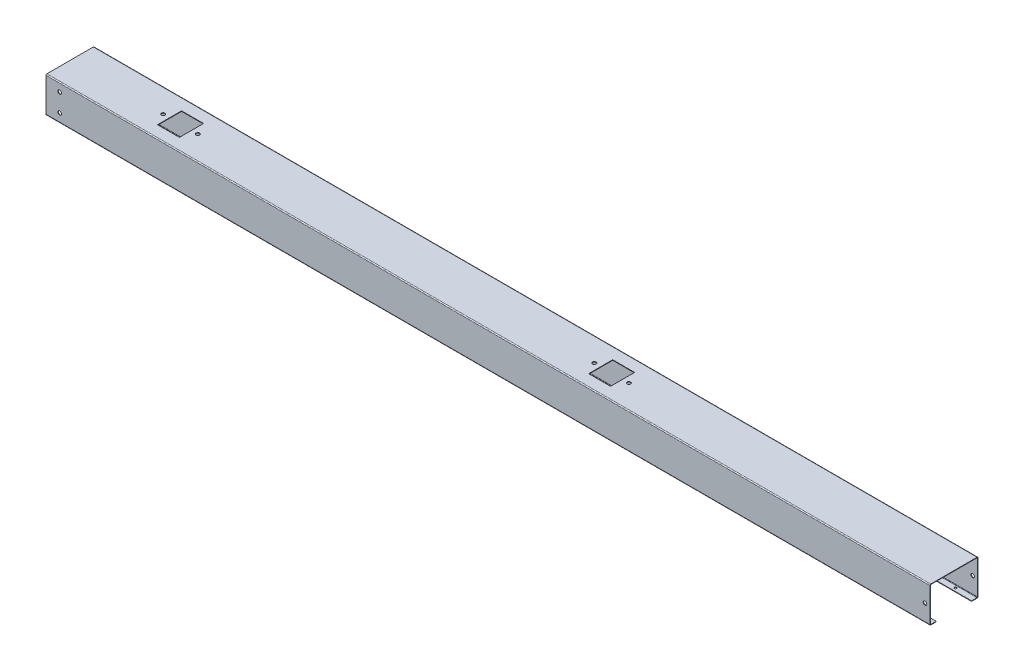
SolidWorks part; units mm, degrees
note: The reader was unsure of these and kept them because the rebuilt part matched: thickness of "Base-Flange1", "Edge-Flange1", "Edge-Flange5", "Sheet-Metal1", "Sheet-Metal2", "Sheet-Metal3", "Sheet-Metal5", "Sheet-Metal15", "Sheet-Metal16", "Sheet-Metal17", "Sheet-Metal22", "Sheet-Metal28", "Sheet-Metal29"; flange length of "Edge-Flange1", "Edge-Flange5".
ref_plane "Front Plane" through (0, 0, 0) normal (0, 0, 1) x (1, 0, 0)
ref_plane "Top Plane" through (0, 0, 0) normal (0, 1, 0) x (1, 0, 0)
ref_plane "Right Plane" through (0, 0, 0) normal (1, 0, 0) x (0, 0, -1)
sketch "Sketch1" plane through (0, 0, 0) normal (0, 1, 0) x (1, 0, 0)
  line L0 (825.5, 38.1) -> (825.5, -38.1)
  line L1 (-571.5, -38.1) -> (825.5, -38.1)
  line L2 (-571.5, -38.1) -> (-571.5, 38.1)
  line L3 (-571.5, 38.1) -> (825.5, 38.1)
  point P0 (0, 0)
  dimension "D1" = 1397
  dimension "D2" = 76.2
base flange "Base-Flange1" sketch "Sketch1" thickness 0.7595 reverse thickness direction no parameters "D1"=0.7366
sketch "Sketch6" plane through (0, 0, 0) normal (0, 1, 0) x (1, 0, 0)
  line L1 (-414.3375, -19.05) -> (-390.7165, -19.05)
  line L2 (-414.3375, -19.05) -> (-414.3375, 19.05)
  line L3 (-414.3375, 19.05) -> (-390.7165, 19.05)
  line L4 (-379.6665, -19.05) -> (-379.6665, 19.05)
  line L5 (-414.3375, -19.05) -> (-379.6665, 19.05) construction
  line L6 (-414.3375, 19.05) -> (-379.6665, -19.05) construction
  line L7 (267.1445, -19.05) -> (290.7655, -19.05)
  line L8 (267.1445, -19.05) -> (267.1445, 19.05)
  line L9 (267.1445, 19.05) -> (290.7655, 19.05)
  line L10 (301.8155, -19.05) -> (301.8155, 19.05)
  line L11 (267.1445, -19.05) -> (301.8155, 19.05) construction
  line L12 (267.1445, 19.05) -> (301.8155, -19.05) construction
  line L13 (-390.7165, 19.05) -> (-379.6665, 19.05)
  line L14 (-390.7165, -19.05) -> (-379.6665, -19.05)
  line L15 (290.7655, 19.05) -> (301.8155, 19.05)
  line L16 (290.7655, -19.05) -> (301.8155, -19.05)
  line L17 (-571.5, 38.1) -> (-571.5, -38.1) construction
  point P0 (-397.002, 0)
  point P6 (284.48, 0)
  point P15 (-414.3375, 0)
  point P19 (267.1445, 0)
  point P23 (-379.6665, 0)
  point P28 (301.8155, 0)
  dimension "D1" = 34.671
  dimension "D2" = 38.1
  dimension "D3" = 34.671
  dimension "D4" = 38.1
  dimension "D5" = 174.498
  dimension "D6" = 681.482
extrude "Cut-Extrude1" cut sketch "Sketch6" against normal blind 10 normal cut yes
sketch "Sketch7" plane through (0, 0, 0) normal (0, 1, 0) x (1, 0, 0)
  line L0 (-414.3375, 19.05) -> (-414.3375, -19.05) construction
  line L1 (-379.6665, -19.05) -> (-379.6665, 19.05) construction
  line L2 (267.1445, -19.05) -> (267.1445, 19.05) construction
  line L4 (301.8155, -19.05) -> (301.8155, 19.05) construction
  circle A0 centre (-424.3375, 0) radius 2.8194
  circle A1 centre (-369.6665, 0) radius 2.8194
  circle A4 centre (257.1445, 0) radius 2.8194
  circle A5 centre (311.8155, 0) radius 2.8194
  dimension "D1" = 5.6388
  dimension "D2" = 10
  dimension "D4" = 5.6388
  dimension "D8" = 5.6388
  dimension "D9" = 5.6388
  dimension "D3" = 10
  dimension "D5" = 10
  dimension "D7" = 10
extrude "Cut-Extrude2" cut sketch "Sketch7" against normal blind 10 normal cut yes
edge flange "Edge-Flange1" sketch "Sketch37" flange profiles "Sketch37", "Sketch39" flange angle 90 flange length 55.372 flange position material inside bend radius 0.7366 thickness 0.7595 relief rectangular parameters "D6"=10, "D8"=0.254
sketch "Sketch37" plane through (0, -0.7595, -38.1) normal (0, 0, -1) x (1, 0, 0)
  line L0 (825.5, 0) -> (-571.5, 0) construction
  line L1 (825.5, 0) -> (-571.5, 0)
  line L2 (-571.5, 0) -> (-571.5, 54.6125)
  line L3 (-571.5, 54.6125) -> (825.5, 54.6125)
  line L4 (825.5, 54.6125) -> (825.5, 0)
sketch "Sketch39" plane through (0, -0.7595, 38.1) normal (0, 0, 1) x (-1, 0, 0)
  line L0 (571.5, 0) -> (-825.5, 0) construction
  line L1 (571.5, 0) -> (-825.5, 0)
  line L2 (-825.5, 0) -> (-825.5, 54.6125)
  line L3 (-825.5, 54.6125) -> (571.5, 54.6125)
  line L4 (571.5, 54.6125) -> (571.5, 0)
bend "EdgeBend8" bend radius 0.7366 bend angle 90 parameters "D5"=4
bend "EdgeBend9" bend radius 0.7366 bend angle 90 parameters "D5"=5
sketch "Sketch40" plane through (0, 0, -38.1) normal (0, 0, -1) x (-1, 0, 0)
  line L0 (543.46, -13.448) -> (556.16, -13.448) construction
  line L1 (543.46, -10.6286) -> (556.16, -10.6286)
  line L2 (543.46, -16.2674) -> (556.16, -16.2674)
  line L3 (571.5, -1.4961) -> (571.5, 0) construction
  line L4 (571.5, -55.372) -> (571.5, -1.4961) construction
  arc A0 (543.46, -10.6286) -> (543.46, -16.2674) centre (543.46, -13.448) ccw
  arc A1 (556.16, -16.2674) -> (556.16, -10.6286) centre (556.16, -13.448) ccw
  point P2 (549.81, -13.448)
  point P9 (571.5, -0.748)
  dimension "D1" = 12.7
  dimension "D2" = 5.6388
  dimension "D3" = 12.7
  dimension "D4" = 21.69
extrude "Cut-Extrude3" [suppressed] cut sketch "Sketch40" against normal through all both and the other way through all
sketch "Sketch42" plane through (0, 0, 38.1) normal (0, 0, 1) x (1, 0, 0)
  line L0 (-571.5, -1.4961) -> (-571.5, -55.372) construction
  line L1 (-571.5, -55.372) -> (825.5, -55.372) construction
  circle A0 centre (-127, -21.082) radius 2.8194
  circle A1 centre (-76.2, -21.082) radius 2.8194
  dimension "D3" = 5.6388
  dimension "D1" = 444.5
  dimension "D2" = 34.29
  dimension "D4" = 50.8
extrude "Cut-Extrude4" [suppressed] cut sketch "Sketch42" against normal up to next
sketch "Sketch43" plane through (0, 0, -38.1) normal (0, 0, -1) x (-1, 0, 0)
  line L0 (571.5, -55.372) -> (571.5, -1.4961) construction
  line L1 (571.5, -1.4961) -> (571.5, 0) construction
  line L2 (-825.5, -55.372) -> (571.5, -55.372) construction
  circle A0 centre (549.91, -13.448) radius 2.8194
  circle A1 centre (549.91, -42.164) radius 2.8194
  point P6 (571.5, -0.748)
  dimension "D3" = 5.6388
  dimension "D1" = 21.59
  dimension "D2" = 12.7
  dimension "D4" = 21.59
  dimension "D5" = 13.208
extrude "Cut-Extrude5" cut sketch "Sketch43" against normal through all both and the other way through all normal cut yes
edge flange "Edge-Flange5" sketch "Sketch85" flange profiles "Sketch85", "Sketch87" flange angle 90 flange length 10.16 flange position material outside bend radius 0.7366 thickness 0.7595 relief rectangular parameters "D6"=10, "D8"=0.254
sketch "Sketch85" plane through (0, -55.372, 37.3405) normal (0, 1, 0) x (1, 0, 0)
  line L2 (-571.5, 0) -> (-571.5, 9.4005)
  line L3 (-571.5, 9.4005) -> (825.5, 9.4005)
  line L4 (825.5, 9.4005) -> (825.5, 0)
  line L5 (825.5, 0) -> (-571.5, 0) construction
  line L6 (825.5, 0) -> (-571.5, 0)
sketch "Sketch87" plane through (0, -55.372, -37.3405) normal (0, 1, 0) x (-1, 0, 0)
  line L0 (571.5, 0) -> (-825.5, 0) construction
  line L1 (571.5, 0) -> (-825.5, 0)
  line L2 (571.5, 0) -> (571.5, 9.4005)
  line L3 (571.5, 9.4005) -> (-825.5, 9.4005)
  line L4 (-825.5, 9.4005) -> (-825.5, 0)
bend "EdgeBend15" bend radius 0.7366 bend angle 90 parameters "D5"=6
bend "EdgeBend16" bend radius 0.7366 bend angle 90 parameters "D5"=8
sketch "Sketch133" plane through (0, -56.1315, 0) normal (0, -1, 0) x (1, 0, 0)
  line L0 (825.5, 36.6039) -> (825.5, 27.94) construction
  line L1 (825.5, 36.6039) -> (-571.5, 36.6039) construction
  line L2 (825.5, -36.6039) -> (-571.5, -36.6039) construction
  circle A0 centre (698.5, -32.7939) radius 1.651
  circle A1 centre (698.5, 32.7939) radius 1.651
  circle A2 centre (201.93, 32.7939) radius 1.651
  circle A3 centre (201.93, -32.7939) radius 1.651
  circle A4 centre (-238.76, -32.7939) radius 1.651
  circle A5 centre (-238.76, 32.7939) radius 1.651
  circle A6 centre (-467.36, 32.7939) radius 1.651
  circle A7 centre (-467.36, -32.7939) radius 1.651
  circle A8 centre (-535.94, 32.7939) radius 1.651
  circle A9 centre (-535.94, -32.7939) radius 1.651
  circle A10 centre (795.02, 32.7939) radius 1.651
  circle A11 centre (795.02, -32.7939) radius 1.651
  dimension "D1" = 3.302
  dimension "D2" = 127
  dimension "D3" = 3.81
  dimension "D4" = 3.81
  dimension "D5" = 496.57
  dimension "D6" = 440.69
  dimension "D7" = 228.6
  dimension "D8" = 68.58
  dimension "D9" = 96.52
extrude "Cut-Extrude6" cut sketch "Sketch133" against normal up to next and the other way through all normal cut yes
sketch "Sketch134" plane through (0, 0, -38.1) normal (0, 0, -1) x (-1, 0, 0)
  line L0 (-825.5, -1.4961) -> (-825.5, -54.6354) construction
  line L1 (-825.5, 0) -> (571.5, 0) construction
  circle A0 centre (-817.88, -29.21) radius 2.8194
  dimension "D1" = 5.6388
  dimension "D2" = 7.62
  dimension "D3" = 29.21
extrude "Cut-Extrude7" cut sketch "Sketch134" against normal through all both and the other way through all normal cut yes
sketch "Bend-Lines1" [suppressed] plane through (0, 0, 0) normal (0, 1, 0) x (1, 0, 0)
sketch "Bounding-Box1" [suppressed] plane through (0, 0, 0) normal (0, 1, 0) x (1, 0, 0)
sheet metal parameters "Sheet-Metal1" thickness 0.7595 parameters "D1"=0.7366
flat pattern "Flat-Pattern1" [suppressed]
sketch "Bend-Lines2" plane through (0, 0, 0) normal (0, 1, 0) x (1, 0, 0)
sketch3d "Bounding-Box2" [suppressed]
  line L0 (25, 20, 0) -> (-25, 20, 0) construction
  line L1 (25, -20, 0) -> (-25, -20, 0) construction
  line L2 (25, 20, 0) -> (25, -20, 0) construction
  line L3 (-25, 20, 0) -> (-25, -20, 0) construction
sheet metal parameters "Sheet-Metal2" thickness 0.7595 parameters "D1"=0.7366, "D7"=1.7366
flat pattern "Flat-Pattern1"
sketch "Bend-Lines2" plane through (0, 0, 0) normal (0, 1, 0) x (1, 0, 0)
sketch3d "Bounding-Box2" [suppressed]
  line L0 (50, 25, 0) -> (-50, 25, 0) construction
  line L1 (50, -25, 0) -> (-50, -25, 0) construction
  line L2 (50, 25, 0) -> (50, -25, 0) construction
  line L3 (-50, 25, 0) -> (-50, -25, 0) construction
sheet metal parameters "Sheet-Metal3" thickness 0.7595 parameters "D1"=0.7366, "D7"=1.7366
flat pattern "Flat-Pattern1"
sketch "Bend-Lines2" plane through (0, 0, 0) normal (0, 1, 0) x (1, 0, 0)
sketch3d "Bounding-Box2" [suppressed]
  line L0 (571.5, 31.75, 0) -> (-571.5, 31.75, 0) construction
  line L1 (571.5, -31.75, 0) -> (-571.5, -31.75, 0) construction
  line L2 (571.5, 31.75, 0) -> (571.5, -31.75, 0) construction
  line L3 (-571.5, 31.75, 0) -> (-571.5, -31.75, 0) construction
sheet metal parameters "Sheet-Metal5" thickness 0.7595 parameters "D1"=0.7366, "D7"=1.7366
flat pattern "Flat-Pattern1"
sketch "Bend-Lines2" plane through (0, 0, 0) normal (0, 1, 0) x (1, 0, 0)
  line L0 (570.8807, -37.1609) -> (570.8807, 37.1609) construction
  line L1 (570.8807, -37.1609) -> (570.8807, 37.1609) construction
  line L2 (-571.5, -37.4807) -> (570.5609, -37.4807) construction
  line L3 (570.5609, 37.4807) -> (-571.5, 37.4807) construction
  line L5 (-571.5, -37.4807) -> (570.5609, -37.4807) construction
  line L6 (570.5609, 37.4807) -> (-571.5, 37.4807) construction
  point P6 (-570.8807, 37.1609)
  point P7 (-570.8807, -37.1609)
sketch3d "Bounding-Box2" [suppressed]
  line L0 (627.4114, 94.0114, 0) -> (-571.5, 94.0114, 0) construction
  line L1 (627.4114, -94.0114, 0) -> (-571.5, -94.0114, 0) construction
  line L2 (627.4114, 94.0114, 0) -> (627.4114, -94.0114, 0) construction
  line L3 (-571.5, 94.0114, 0) -> (-571.5, -94.0114, 0) construction
bend of the flat pattern "Flatten-<EdgeBend8>1"
bend of the flat pattern "Flatten-<EdgeBend9>1"
sheet metal parameters "Sheet-Metal15" thickness 0.7595 parameters "D1"=0.7366, "D7"=1.7366
flat pattern "Flat-Pattern1"
sketch "Bend-Lines2" plane through (0, 0, 0) normal (0, 1, 0) x (1, 0, 0)
  line L2 (-571.5, -37.4807) -> (571.5, -37.4807) construction
  line L3 (571.5, 37.4807) -> (-571.5, 37.4807) construction
  line L5 (-571.5, -37.4807) -> (571.5, -37.4807) construction
  line L6 (571.5, 37.4807) -> (-571.5, 37.4807) construction
sketch3d "Bounding-Box2" [suppressed]
  line L0 (571.5, 94.0114, 0) -> (-571.5, 94.0114, 0) construction
  line L1 (571.5, -94.0114, 0) -> (-571.5, -94.0114, 0) construction
  line L2 (571.5, 94.0114, 0) -> (571.5, -94.0114, 0) construction
  line L3 (-571.5, 94.0114, 0) -> (-571.5, -94.0114, 0) construction
bend of the flat pattern "Flatten-<EdgeBend8>1"
bend of the flat pattern "Flatten-<EdgeBend9>1"
sheet metal parameters "Sheet-Metal16" thickness 0.7595 parameters "D1"=0.7366, "D7"=1.7366
flat pattern "Flat-Pattern1"
sketch "Bend-Lines2" plane through (0, 0, 0) normal (0, 1, 0) x (1, 0, 0)
  line L2 (-571.5, -37.4807) -> (571.5, -37.4807) construction
  line L3 (571.5, 37.4807) -> (-571.5, 37.4807) construction
  line L5 (-571.5, -37.4807) -> (571.5, -37.4807) construction
  line L6 (571.5, 37.4807) -> (-571.5, 37.4807) construction
sketch3d "Bounding-Box2" [suppressed]
  line L0 (571.5, 94.0114, 0) -> (-571.5, 94.0114, 0) construction
  line L1 (571.5, -94.0114, 0) -> (-571.5, -94.0114, 0) construction
  line L2 (571.5, 94.0114, 0) -> (571.5, -94.0114, 0) construction
  line L3 (-571.5, 94.0114, 0) -> (-571.5, -94.0114, 0) construction
bend of the flat pattern "Flatten-<EdgeBend8>1"
bend of the flat pattern "Flatten-<EdgeBend9>1"
sheet metal parameters "Sheet-Metal17" thickness 0.7595 parameters "D1"=0.7366, "D7"=1.7366
flat pattern "Flat-Pattern1"
sketch "Bend-Lines2" plane through (0, 0, 0) normal (0, 1, 0) x (1, 0, 0)
  line L2 (-571.5, -37.4807) -> (571.5, -37.4807) construction
  line L3 (571.5, 37.4807) -> (-571.5, 37.4807) construction
  line L5 (-571.5, -37.4807) -> (571.5, -37.4807) construction
  line L6 (571.5, 37.4807) -> (-571.5, 37.4807) construction
sketch3d "Bounding-Box2" [suppressed]
  line L0 (571.5, 94.0114, 0) -> (-571.5, 94.0114, 0) construction
  line L1 (571.5, -94.0114, 0) -> (-571.5, -94.0114, 0) construction
  line L2 (571.5, 94.0114, 0) -> (571.5, -94.0114, 0) construction
  line L3 (-571.5, 94.0114, 0) -> (-571.5, -94.0114, 0) construction
bend of the flat pattern "Flatten-<EdgeBend8>1"
bend of the flat pattern "Flatten-<EdgeBend9>1"
sheet metal parameters "Sheet-Metal22" thickness 0.7595 parameters "D1"=0.7366, "D7"=1.7366
flat pattern "Flat-Pattern1"
sketch "Bend-Lines2" plane through (0, 0, 0) normal (0, 1, 0) x (1, 0, 0)
  line L0 (-571.5, -93.6436) -> (571.5, -93.6436) construction
  line L1 (-571.5, -93.6436) -> (571.5, -93.6436) construction
  line L2 (-571.5, -37.4807) -> (571.5, -37.4807) construction
  line L3 (571.5, 37.4807) -> (-571.5, 37.4807) construction
  line L4 (571.5, 93.6436) -> (-571.5, 93.6436) construction
  line L5 (-571.5, -37.4807) -> (571.5, -37.4807) construction
  line L6 (571.5, 37.4807) -> (-571.5, 37.4807) construction
  line L7 (571.5, 93.6436) -> (-571.5, 93.6436) construction
sketch3d "Bounding-Box2" [suppressed]
  line L0 (571.5, 103.1843, 0) -> (-571.5, 103.1843, 0) construction
  line L1 (571.5, -103.1843, 0) -> (-571.5, -103.1843, 0) construction
  line L2 (571.5, 103.1843, 0) -> (571.5, -103.1843, 0) construction
  line L3 (-571.5, 103.1843, 0) -> (-571.5, -103.1843, 0) construction
bend of the flat pattern "Flatten-<EdgeBend8>1"
bend of the flat pattern "Flatten-<EdgeBend9>1"
bend of the flat pattern "Flatten-<EdgeBend15>1"
bend of the flat pattern "Flatten-<EdgeBend16>1"
sheet metal parameters "Sheet-Metal28" thickness 0.7595 parameters "D1"=0.7366, "D7"=1.7366
flat pattern "Flat-Pattern1"
sketch "Bend-Lines2" plane through (0, 0, 0) normal (0, 1, 0) x (1, 0, 0)
  line L0 (-571.5, -93.6436) -> (825.5, -93.6436) construction
  line L1 (-571.5, -93.6436) -> (825.5, -93.6436) construction
  line L2 (-571.5, -37.4807) -> (825.5, -37.4807) construction
  line L3 (825.5, 37.4807) -> (-571.5, 37.4807) construction
  line L4 (825.5, 93.6436) -> (-571.5, 93.6436) construction
  line L5 (-571.5, -37.4807) -> (825.5, -37.4807) construction
  line L6 (825.5, 37.4807) -> (-571.5, 37.4807) construction
  line L7 (825.5, 93.6436) -> (-571.5, 93.6436) construction
sketch3d "Bounding-Box2" [suppressed]
  line L0 (825.5, 103.1843, 0) -> (-571.5, 103.1843, 0) construction
  line L1 (825.5, -103.1843, 0) -> (-571.5, -103.1843, 0) construction
  line L2 (825.5, 103.1843, 0) -> (825.5, -103.1843, 0) construction
  line L3 (-571.5, 103.1843, 0) -> (-571.5, -103.1843, 0) construction
bend of the flat pattern "Flatten-<EdgeBend8>1"
bend of the flat pattern "Flatten-<EdgeBend9>1"
bend of the flat pattern "Flatten-<EdgeBend15>1"
bend of the flat pattern "Flatten-<EdgeBend16>1"
sheet metal parameters "Sheet-Metal29" thickness 0.7595 parameters "D1"=0.7366, "D7"=1.7366
flat pattern "Flat-Pattern1"
sketch "Bend-Lines2" plane through (0, 0, 0) normal (0, 1, 0) x (1, 0, 0)
  line L0 (-571.5, -92.3736) -> (825.5, -92.3736) construction
  line L1 (-571.5, -92.3736) -> (825.5, -92.3736) construction
  line L2 (-571.5, -37.4807) -> (825.5, -37.4807) construction
  line L3 (825.5, 37.4807) -> (-571.5, 37.4807) construction
  line L4 (825.5, 92.3736) -> (-571.5, 92.3736) construction
  line L5 (-571.5, -37.4807) -> (825.5, -37.4807) construction
  line L6 (825.5, 37.4807) -> (-571.5, 37.4807) construction
  line L7 (825.5, 92.3736) -> (-571.5, 92.3736) construction
sketch3d "Bounding-Box2" [suppressed]
  line L0 (825.5, 101.9143, 0) -> (-571.5, 101.9143, 0) construction
  line L1 (825.5, -101.9143, 0) -> (-571.5, -101.9143, 0) construction
  line L2 (825.5, 101.9143, 0) -> (825.5, -101.9143, 0) construction
  line L3 (-571.5, 101.9143, 0) -> (-571.5, -101.9143, 0) construction
bend of the flat pattern "Flatten-<EdgeBend8>1"
bend of the flat pattern "Flatten-<EdgeBend9>1"
bend of the flat pattern "Flatten-<EdgeBend15>1"
bend of the flat pattern "Flatten-<EdgeBend16>1"
